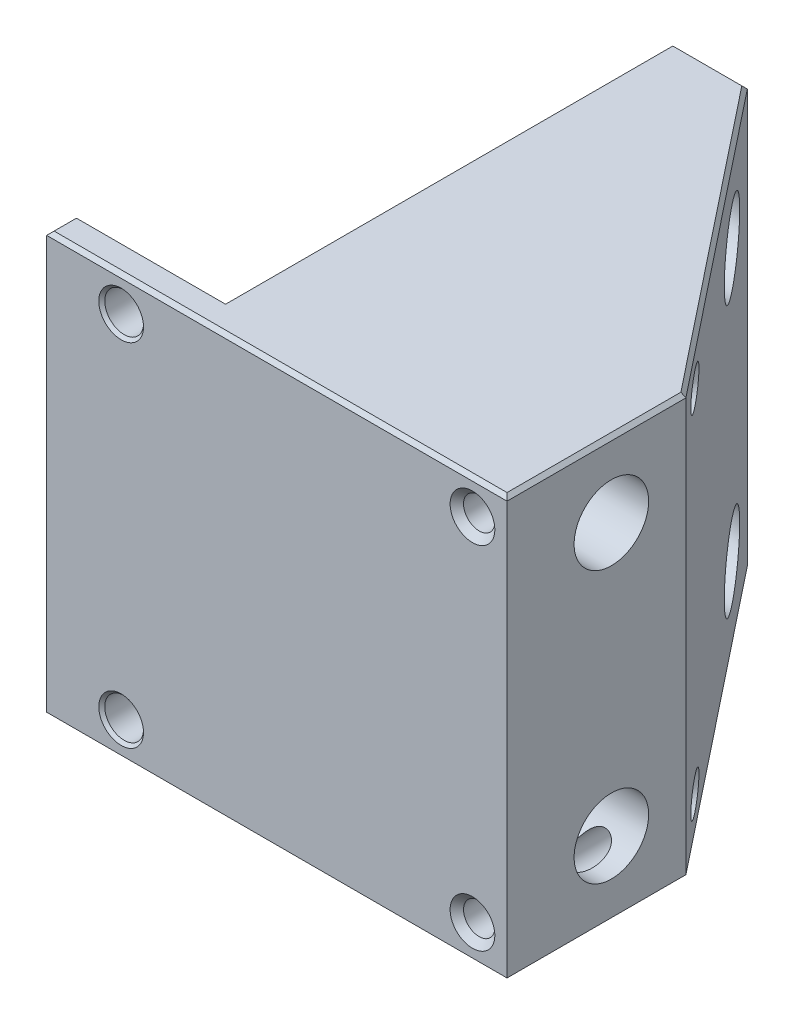
SolidWorks part; units mm, degrees
ref_plane "Front Plane" through (0, 0, 0) normal (0, 0, 1) x (1, 0, 0)
ref_plane "Top Plane" through (0, 0, 0) normal (0, 1, 0) x (1, 0, 0)
ref_plane "Right Plane" through (0, 0, 0) normal (1, 0, 0) x (0, 0, -1)
sketch "Sketch1" plane through (0, 0, 0) normal (0, 0, 1) x (1, 0, 0)
  line L1 (-30.88, 28.2) -> (30.88, 28.2)
  line L2 (-30.88, 28.2) -> (-30.88, -28.2)
  line L3 (-30.88, -28.2) -> (30.88, -28.2)
  line L4 (30.88, 28.2) -> (30.88, -28.2)
  line L5 (-30.88, 28.2) -> (30.88, -28.2) construction
  line L6 (-30.88, -28.2) -> (30.88, 28.2) construction
  point P0 (0, 0)
  dimension "D1" = 56.4
  dimension "D2" = 61.76
extrude "Boss-Extrude1" add sketch "Sketch1" along normal blind 4
sketch "Sketch9" plane through (0, 0, 4) normal (0, 0, 1) x (1, 0, 0)
  line L0 (30.88, 0) -> (2.68, 0) construction
  line L1 (30.88, -28.2) -> (30.88, 28.2) construction
  line L2 (2.68, 0) -> (2.68, 28.2) construction
  line L3 (30.88, 28.2) -> (-30.88, 28.2) construction
  circle A0 centre (2.68, 0) radius 2.5
  dimension "D1" = 5
sketch "Sketch12" plane through (0, 0, 4) normal (0, 0, 1) x (1, 0, 0)
  line L1 (26.245, 23.565) -> (-20.885, 23.565)
  line L2 (26.245, 23.565) -> (26.245, -23.565)
  line L3 (26.245, -23.565) -> (-20.885, -23.565)
  line L4 (-20.885, 23.565) -> (-20.885, -23.565)
  line L5 (26.245, 23.565) -> (-20.885, -23.565) construction
  line L6 (26.245, -23.565) -> (-20.885, 23.565) construction
  point P0 (2.68, 0)
  point P6 (4.5801, 8.5883)
  point P7 (2.68, 0)
  point P9 (2.68, 0)
  dimension "D1" = 47.13
hole_wizard "M5x0.8 Tapped Hole1" positions "Sketch13" profile "Sketch15" tap size "M5x0.8" standard "ANSI Metric" end condition through all
sketch "Sketch13" plane through (0, 0, 4) normal (0, 0, 1) x (1, 0, 0)
  point P0 (26.245, 23.565)
  point P3 (26.245, -23.565)
  point P6 (-20.885, -23.565)
  point P9 (-20.885, 23.565)
sketch "Sketch15" plane through (26.245, 23.565, 4) normal (1, 0, 0) x (0, -1, 0)
  line L0 (0, 0) -> (0, 4)
  line L1 (0, 4) -> (2.1, 4)
  line L2 (2.1, 4) -> (2.1, 0.9)
  line L3 (2.1, 0.9) -> (3, 0)
  line L5 (3, 0) -> (0, 0)
  line L6 (-2.1, 0.9) -> (-3, 0) construction
  line L11 (0, -6.35) -> (0, 107.95) construction
  dimension "Thru Tap Drill Dia." = 4.2
  dimension "Thru Tap Drill Depth" = 4
  dimension "Near C'Sink Dia." = 6
  dimension "Near C'Sink Angle" = 90
cosmetic thread "Hole Thread1" parameters "D2"=5
cosmetic thread "Hole Thread2" parameters "D2"=5
cosmetic thread "Hole Thread3" parameters "D2"=5
cosmetic thread "Hole Thread4" parameters "D2"=5
sketch "Sketch37" plane through (0, 0, 0) normal (0, 0, -1) x (-1, 0, 0)
  line L0 (-30.88, 28.2) -> (30.88, 28.2) construction
  line L1 (-30.88, -28.2) -> (10.88, -28.2)
  line L2 (-30.88, -28.2) -> (-30.88, 28.2)
  line L3 (-30.88, 28.2) -> (10.88, 28.2)
  line L4 (10.88, -28.2) -> (10.88, 28.2)
  line L5 (30.88, 28.2) -> (30.88, -28.2) construction
  circle A0 centre (-26.245, 23.565) radius 2.1 construction
  circle A1 centre (-26.245, -23.565) radius 2.1 construction
  circle A2 centre (-26.245, 23.565) radius 2.1
  circle A3 centre (-26.245, -23.565) radius 2.1
  dimension "D1" = 20
extrude "Boss-Extrude7" add sketch "Sketch37" along normal blind 60
sketch "Sketch39" plane through (0, 0, 4) normal (0, 0, 1) x (1, 0, 0)
  circle A0 centre (-20.885, -23.565) radius 2.6
  circle A1 centre (-20.885, 23.565) radius 2.6
  dimension "D1" = 5.2
extrude "Cut-Extrude1" cut sketch "Sketch39" against normal through all
sketch "Sketch40" plane through (0, -28.2, 0) normal (0, -1, 0) x (1, 0, 0)
  line L0 (-0.88, -60) -> (30.88, -20)
  line L1 (30.88, -60) -> (-10.88, -60) construction
  line L2 (30.88, 4) -> (30.88, -60) construction
  line L3 (30.88, -20) -> (30.88, -60)
  line L4 (30.88, -60) -> (-0.88, -60)
  line L5 (-30.88, 0) -> (-10.88, 0) construction
  line L6 (-10.88, -60) -> (-10.88, 0) construction
  dimension "D1" = 20
  dimension "D2" = 10
extrude "Cut-Extrude2" cut sketch "Sketch40" against normal through all
sketch "Sketch41" plane through (30.88, 0, 0) normal (1, 0, 0) x (0, 0, -1)
  line L0 (60, 28.2) -> (60, -28.2) construction
  line L1 (10, -18.2) -> (50, -18.2)
  line L2 (10, -18.2) -> (10, 18.2)
  line L3 (10, 18.2) -> (50, 18.2)
  line L4 (50, -18.2) -> (50, 18.2)
  line L6 (-4, -28.2) -> (20, -28.2) construction
  line L7 (-4, 28.2) -> (20, 28.2) construction
  line L8 (0, -28.2) -> (0, 28.2) construction
  dimension "D1" = 10
  dimension "D2" = 10
  dimension "D3" = 10
  dimension "D4" = 10
hole_wizard "CBORE for M5 SHCS3" positions "Sketch42" profile "Sketch44" counterbore size "M5" standard "ANSI Metric" end condition through all
sketch "Sketch42" plane through (30.88, 0, 0) normal (1, 0, 0) x (0, 0, -1)
  point P0 (10, -18.2)
  point P3 (10, 18.2)
  point P6 (50, 18.2)
  point P9 (50, -18.2)
sketch "Sketch44" plane through (30.88, -18.2, -10) normal (0, 1, 0) x (0, 0, -1)
  line L0 (0, 0) -> (0, 61.76)
  line L1 (0, 61.76) -> (2.75, 61.76)
  line L3 (2.75, 61.76) -> (2.75, 36.7)
  line L4 (2.75, 36.7) -> (5, 36.7)
  line L5 (5, 36.7) -> (5, 0)
  line L7 (5, 0) -> (0, 0)
  line L11 (0, -6.35) -> (0, 107.95) construction
  dimension "Thru Hole Dia." = 5.5
  dimension "Thru Hole Depth" = 61.76
  dimension "C'Bore Dia." = 10
  dimension "C'Bore Depth" = 36.7
chamfer "Chamfer7" distance 0.5 angle 45 14 edges at (0, 28.2, 4) (-30.88, 28.2, 2) (-20.88, 28.2, 0) (-10.88, 28.2, -30) (-5.88, 28.2, -60) (15, 28.2, -40) (30.88, 28.2, -8) (-10.88, -28.2, -30) (-20.88, -28.2, 0) (-30.88, -28.2, 2) (0, -28.2, 4) (30.88, -28.2, -8) (15, -28.2, -40) (-5.88, -28.2, -60)
